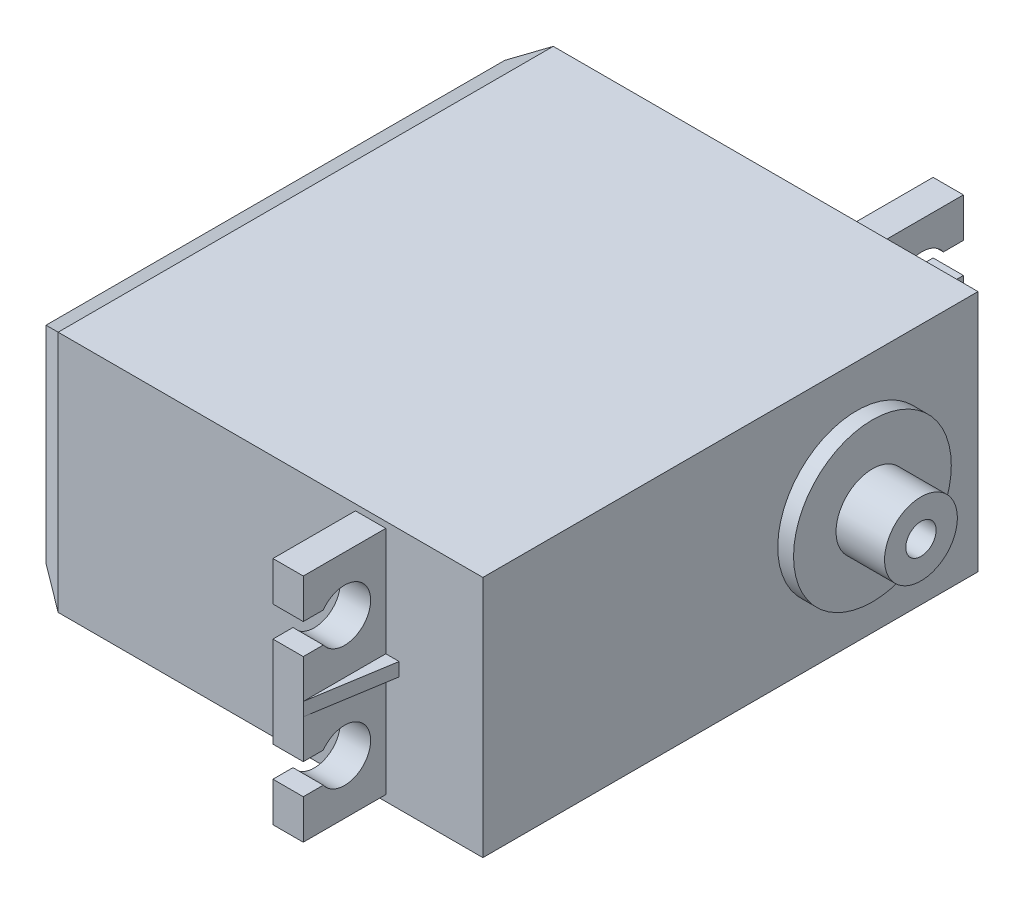
SolidWorks part; units mm, degrees
material "PP Kopolymer"
ref_plane "Ebene vorne" through (0, 0, 0) normal (0, 0, 1) x (1, 0, 0)
ref_plane "Ebene oben" through (0, 0, 0) normal (0, 1, 0) x (1, 0, 0)
ref_plane "Ebene rechts" through (0, 0, 0) normal (1, 0, 0) x (0, 0, -1)
sketch "Skizze1" plane through (0, 0, 0) normal (0, 0, 1) x (1, 0, 0)
  line L0 (0, 0) -> (-10.095, 0) construction
  line L1 (-18.75, 10) -> (18.75, 10)
  line L2 (-18.75, 10) -> (-18.75, -10)
  line L3 (-18.75, -10) -> (18.75, -10)
  line L4 (18.75, 10) -> (18.75, -10)
  line L5 (0, 0) -> (0, 6.0195) construction
  dimension "D1" = 20
  dimension "D2" = 37.5
extrude "Aufsatz-Linear austragen1" add sketch "Skizze1" along normal blind 40.8
sketch "Skizze2" plane through (0, 0, 40.8) normal (0, 0, 1) x (1, 0, 0)
  line L0 (18.75, -10) -> (18.75, 10) construction
  line L1 (8.25, -9.5) -> (10.75, -9.5)
  line L2 (8.25, -9.5) -> (8.25, 9.5)
  line L3 (8.25, 9.5) -> (10.75, 9.5)
  line L4 (10.75, -9.5) -> (10.75, 9.5)
  line L5 (8.25, -9.5) -> (10.75, 9.5) construction
  line L6 (8.25, 9.5) -> (10.75, -9.5) construction
  point P0 (9.5, 0)
  dimension "D1" = 19
  dimension "D2" = 2.5
  dimension "D3" = 8
extrude "Aufsatz-Linear austragen2" add sketch "Skizze2" along normal blind 6.8
hole_wizard "Ø4.3 (4.3) Diameter Hole2" positions "Skizze4" profile "Skizze3" hole size "Ø4.3" standard "DIN"
sketch "Skizze4" plane through (10.75, 0, 0) normal (1, 0, 0) x (0, 0, -1)
  line L0 (-47.6, -9.5) -> (-47.6, 9.5) construction
  line L2 (-44.2, 5) -> (-44.2, -5) construction
  line L4 (-44.2, 0) -> (0, 0) construction
  point P0 (-44.2, 5)
  point P2 (-44.2, -5)
  dimension "D1" = 10
  dimension "D2" = 3.4
sketch "Skizze3" plane through (10.75, 5, 44.2) normal (0, 1, 0) x (0, 0, -1)
  line L0 (0, 0) -> (0, 11.2919)
  line L1 (0, 11.2919) -> (2.15, 10)
  line L2 (2.15, 10) -> (2.15, 0)
  line L5 (2.15, 0) -> (0, 0)
  line L10 (0, 11.2919) -> (-2.15, 10) construction
  line L11 (0, -6.35) -> (0, 107.95) construction
  dimension "Bohrerdurchmesser" = 4.3
  dimension "Bohrungstiefe" = 10
  dimension "Spitzenwinkel" = 118
sketch "Sketch1" plane through (10.75, 0, 0) normal (1, 0, 0) x (0, 0, -1)
  line L0 (-42.05, 5) -> (-44.2, 5) construction
  line L1 (-45.55, 3.75) -> (-48.55, 3.75)
  line L2 (-45.55, 3.75) -> (-45.55, 6.25)
  line L3 (-45.55, 6.25) -> (-48.55, 6.25)
  line L4 (-48.55, 3.75) -> (-48.55, 6.25)
  line L5 (-45.55, 3.75) -> (-48.55, 6.25) construction
  line L6 (-45.55, 6.25) -> (-48.55, 3.75) construction
  line L7 (-40.8, 0) -> (-48.75, 0) construction
  line L8 (-40.8, -10) -> (-40.8, 10) construction
  line L9 (-45.55, -3.75) -> (-45.55, -6.25)
  line L10 (-45.55, -6.25) -> (-48.55, -6.25)
  line L11 (-48.55, -3.75) -> (-48.55, -6.25)
  line L12 (-45.55, -3.75) -> (-48.55, -3.75)
  circle A0 centre (-44.2, 5) radius 2.15 construction
  point P0 (-47.05, 5)
  dimension "D1" = 2.5
  dimension "D2" = 3
  dimension "D3" = 5
extrude "Cut-Extrude1" cut sketch "Sketch1" against normal up to next
ref_plane "Ebene1" through (0, 0, 20.4) normal (0, 0, -1) x (-1, 0, 0)
mirror "Spiegeln2" about plane through (0, 0, 20.4) normal (0, 0, -1) of "Cut-Extrude1", "Aufsatz-Linear austragen2", "Ø4.3 (4.3) Diameter Hole2"
sketch "Sketch3" plane through (0, 0, 0) normal (0, 1, 0) x (1, 0, 0)
  line L0 (10.75, 0) -> (11.85, 0)
  line L1 (11.85, 0) -> (10.75, 6.8)
  line L2 (10.75, 6.8) -> (10.75, 0)
  line L3 (18.75, 0) -> (-18.75, 0) construction
  line L4 (10.75, 6.8) -> (8.25, 6.8) construction
  dimension "D2" = 1.1
extrude "Boss-Extrude1" add sketch "Sketch3" along normal mid plane 1.1
sketch "Skizze5" plane through (18.75, 0, 0) normal (1, 0, 0) x (0, 0, -1)
  line L1 (0, -10) -> (0, 10) construction
  circle A0 centre (-10, 0) radius 6.5
  point P2 (0, 0)
  dimension "D1" = 13
  dimension "D2" = 10
extrude "Aufsatz-Linear austragen3" add sketch "Skizze5" along normal blind 1.3
sketch "Skizze6" plane through (20.05, 0, 0) normal (1, 0, 0) x (0, 0, -1)
  circle A0 centre (-10, 0) radius 3
  dimension "D1" = 6
extrude "Aufsatz-Linear austragen4" add sketch "Skizze6" along normal blind 4
sketch "Skizze7" plane through (0, 0, 0) normal (0, 0, -1) x (-1, 0, 0)
  line L1 (16.25, -3) -> (12.25, -3)
  line L2 (16.25, -3) -> (16.25, 3)
  line L3 (16.25, 3) -> (12.25, 3)
  line L4 (12.25, -3) -> (12.25, 3)
  line L5 (16.25, -3) -> (12.25, 3) construction
  line L6 (16.25, 3) -> (12.25, -3) construction
  line L7 (18.75, 10) -> (18.75, -10) construction
  point P0 (14.25, 0)
  dimension "D1" = 4
  dimension "D2" = 6
  dimension "D3" = 2.5
extrude "Aufsatz-Linear austragen5" add sketch "Skizze7" along normal blind 1.5
sketch "Skizze8" plane through (0, 0, -1.5) normal (0, 0, -1) x (-1, 0, 0)
  line L0 (16.25, -3) -> (16.25, 3) construction
  line L1 (15.6, -2.5) -> (12.9, -2.5)
  line L2 (15.6, -2.5) -> (15.6, 2.5)
  line L3 (15.6, 2.5) -> (12.9, 2.5)
  line L4 (12.9, -2.5) -> (12.9, 2.5)
  line L5 (15.6, -2.5) -> (12.9, 2.5) construction
  line L6 (15.6, 2.5) -> (12.9, -2.5) construction
  line L9 (15.1, 2) -> (13.4, 2)
  line L10 (13.4, -2) -> (13.4, 2)
  line L11 (15.1, -2) -> (13.4, -2)
  line L12 (15.1, -2) -> (15.1, 2)
  point P0 (14.25, 0)
  dimension "D1" = 5
  dimension "D2" = 2.7
  dimension "D3" = 0.65
  dimension "D4" = 0.5
extrude "Aufsatz-Linear austragen6" add sketch "Skizze8" along normal blind 5
hole_wizard "Ø5.0 (5) Diameter Hole1" positions "Skizze11" profile "Skizze10" hole size "Ø5.0" standard "DIN"
sketch "Skizze11" plane through (0, 0, 0) normal (0, 0, -1) x (-1, 0, 0)
  line L0 (18.75, 10) -> (18.75, -10) construction
  point P0 (4.25, 0)
  dimension "D1" = 14.5
sketch "Skizze10" plane through (-4.25, 0, 0) normal (1, 0, 0) x (0, 1, 0)
  line L0 (0, 0) -> (0, 5.0022)
  line L1 (0, 5.0022) -> (2.5, 3.5)
  line L2 (2.5, 3.5) -> (2.5, 0)
  line L5 (2.5, 0) -> (0, 0)
  line L10 (0, 5.0022) -> (-2.5, 3.5) construction
  line L11 (0, -6.35) -> (0, 107.95) construction
  dimension "Bohrerdurchmesser" = 5
  dimension "Bohrungstiefe" = 3.5
  dimension "Spitzenwinkel" = 118
hole_wizard "M3 Gewindebohrung1" positions "Skizze14" profile "Skizze15" tap size "M3" standard "DIN"
sketch "Skizze14" plane through (24.05, 0, 0) normal (1, 0, 0) x (0, 0, -1)
  point P0 (-10, 0)
sketch "Skizze15" plane through (24.05, 0, 10) normal (0, 1, 0) x (0, 0, -1)
  line L0 (0, 0) -> (0, 9.2511)
  line L1 (0, 9.2511) -> (1.25, 8.5)
  line L2 (1.25, 8.5) -> (1.25, 0)
  line L5 (1.25, 0) -> (0, 0)
  line L10 (0, 9.2511) -> (-1.25, 8.5) construction
  line L11 (0, -6.35) -> (0, 107.95) construction
  dimension "Bohrerdurchmesser" = 2.5
  dimension "Bohrungstiefe" = 8.5
  dimension "Spitzenwinkel" = 118
cosmetic thread "Bohrungsgewinde1" parameters "D1"=6, "D2"=3
ref_plane "Ebene2" through (0, 0, 20) normal (0, 0, 1) x (1, 0, 0)
mirror "Mirror1" about plane through (0, 0, 20.4) normal (0, 0, -1) of "Boss-Extrude1"
chamfer "Chamfer1" distance 2.5 distance2 1.5 4 edges at (-18.75, 0, 0) (-18.75, -10, 20.4) (-18.75, 0, 40.8) (-18.75, 10, 20.4) first distance on face at (-6.75, 0, 0) first distance on face at (0, -10, 20.4) first distance on face at (10.4, 0, 40.8) first distance on face at (0, 10, 20.4)
